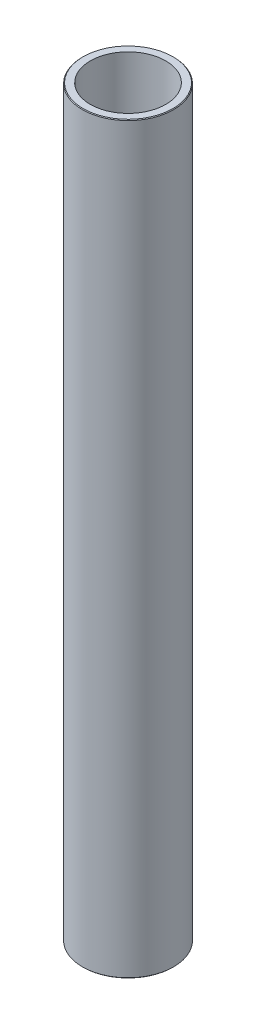
SolidWorks part; units mm, degrees
ref_plane "Front Plane" through (0, 0, 0) normal (0, 0, 1) x (1, 0, 0)
ref_plane "Top Plane" through (0, 0, 0) normal (0, 1, 0) x (1, 0, 0)
ref_plane "Right Plane" through (0, 0, 0) normal (1, 0, 0) x (0, 0, -1)
sketch "Sketch1" plane through (0, 0, 0) normal (0, 1, 0) x (1, 0, 0)
  circle A0 centre (0, 0) radius 32.5
  dimension "SHAFT_OD" = 65
extrude "Boss-Extrude1" add sketch "Sketch1" along normal blind 530.2699
sketch "Sketch2" plane through (0, 0, 0) normal (0, 1, 0) x (1, 0, 0)
  circle A0 centre (0, 0) radius 26.9143
  dimension "BORE_D" = 53.8285
extrude "Cut-Extrude1" cut sketch "Sketch2" along normal through all
chamfer "Chamfer1" distance 0.4744 angle 45 2 edges at (0, 530.2699, 32.5) (0, 0, 32.5)
